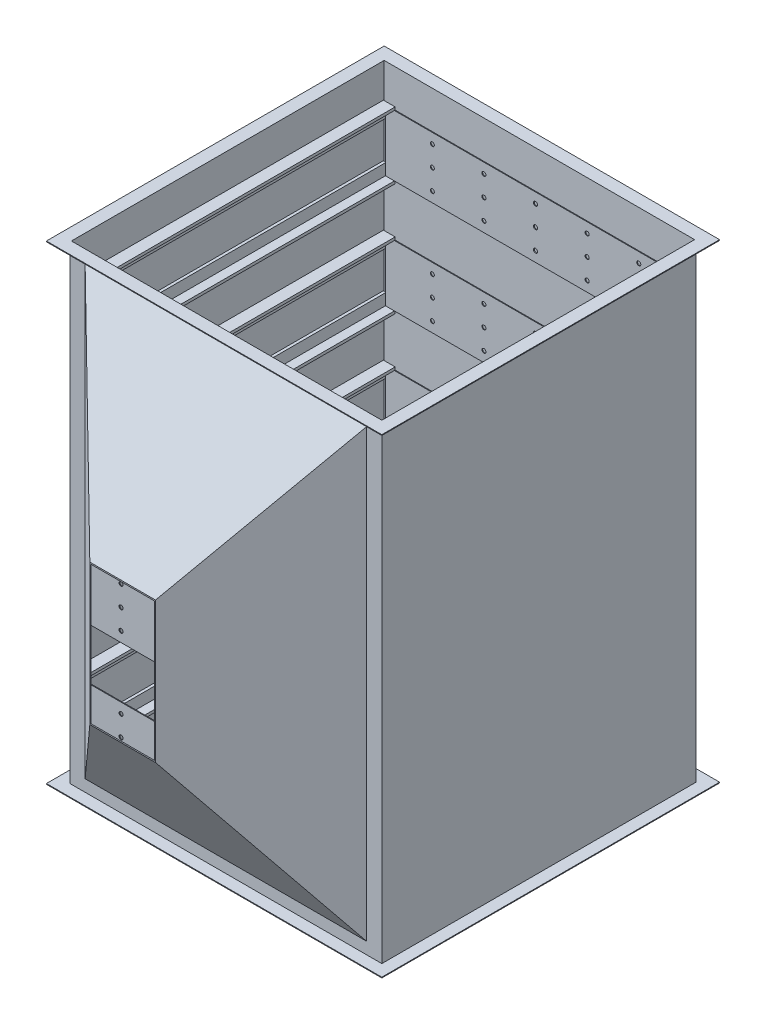
SolidWorks part; units mm, degrees
ref_plane "Front Plane" through (0, 0, 0) normal (0, 0, 1) x (1, 0, 0)
ref_plane "Top Plane" through (0, 0, 0) normal (0, 1, 0) x (1, 0, 0)
ref_plane "Right Plane" through (0, 0, 0) normal (1, 0, 0) x (0, 0, -1)
sketch "Sketch1" plane through (0, 0, 0) normal (0, 0, 1) x (1, 0, 0)
  line L1 (-332.5, -500) -> (332.5, -500)
  line L2 (-332.5, -500) -> (-332.5, 500)
  line L3 (-332.5, 500) -> (332.5, 500)
  line L4 (332.5, -500) -> (332.5, 500)
  line L5 (0, 500) -> (0, -500) construction
  line L6 (-332.5, 0) -> (332.5, 0) construction
  point P0 (0, 0)
  dimension "D1" = 1000
  dimension "D2" = 665
extrude "Boss-Extrude1" add sketch "Sketch1" along normal blind 670
sketch "Sketch2" plane through (0, 0, 670) normal (0, 0, 1) x (1, 0, 0)
  line L1 (-300, -475) -> (300, -475)
  line L2 (-300, -475) -> (-300, 475)
  line L3 (-300, 475) -> (300, 475)
  line L4 (300, -475) -> (300, 475)
  line L5 (0, 475) -> (0, -475) construction
  line L6 (-300, 0) -> (300, 0) construction
  point P0 (0, 0)
  dimension "D1" = 950
  dimension "D2" = 600
ref_plane "Plane1" through (0, 0, 890) normal (0, 0, 1) x (1, 0, 0)
sketch "Sketch3" plane through (0, 0, 890) normal (0, 0, 1) x (1, 0, 0)
  line L1 (-70, -150) -> (70, -150)
  line L2 (-70, -150) -> (-70, 150)
  line L3 (-70, 150) -> (70, 150)
  line L4 (70, -150) -> (70, 150)
  line L5 (0, 150) -> (0, -150) construction
  line L6 (-70, 0) -> (70, 0) construction
  point P0 (0, 0)
  dimension "D1" = 300
  dimension "D2" = 140
loft "Loft1" add profiles "Sketch2", "Sketch3" connector at (-300, 475, 670) connector at (-70, 150, 890)
sketch "Sketch4" plane through (0, 500, 0) normal (0, 1, 0) x (1, 0, 0)
  line L0 (0, 0) -> (0, -670) construction
  line L1 (332.5, 0) -> (-332.5, 0) construction
  line L2 (332.5, -670) -> (-332.5, -670) construction
  line L17 (357.5, -695) -> (357.5, 25)
  line L18 (-357.5, -695) -> (357.5, -695)
  line L19 (-357.5, 25) -> (-357.5, -695)
  line L20 (357.5, 25) -> (-357.5, 25)
  line L21 (357.5, -695) -> (357.5, 25)
  line L22 (-357.5, -695) -> (357.5, -695)
  line L23 (-357.5, 25) -> (-357.5, -695)
  line L24 (357.5, 25) -> (-357.5, 25)
  dimension "D1" = 25
extrude "Boss-Extrude2" add sketch "Sketch4" along normal blind 1.5875
ref_plane "Plano3" through (0, 0, 0) normal (0, -1, 0) x (-1, 0, 0)
mirror "Simetría4" about plane through (0, 0, 0) normal (0, -1, 0) of "Boss-Extrude2"
shell "Shell1" thickness 1.5875 removed face at (0, -501.5875, 335) removed face at (0, 0, 890) removed face at (0, 501.5875, 335)
sketch "Croquis1" plane through (0, 0, 668.4125) normal (0, 0, -1) x (-1, 0, 0)
  line L0 (-325, 401.4331) -> (325, 401.4331) construction
  line L5 (-325, 423.0998) -> (325, 423.0998)
  line L6 (-325, 423.0998) -> (-325, 379.7664)
  line L7 (-325, 379.7664) -> (325, 379.7664) construction
  line L8 (325, 423.0998) -> (325, 379.7664)
  line L9 (-107, 423.0998) -> (-107, 293.0998) construction
  line L26 (-325, 379.7664) -> (325, 379.7664) construction
  line L27 (-325, 379.7664) -> (-325, 336.4331)
  line L28 (-325, 336.4331) -> (325, 336.4331) construction
  line L29 (325, 379.7664) -> (325, 336.4331)
  line L30 (-325, 336.4331) -> (325, 336.4331) construction
  line L31 (-325, 336.4331) -> (-325, 293.0998)
  line L32 (-325, 293.0998) -> (325, 293.0998)
  line L33 (325, 336.4331) -> (325, 293.0998)
  line L34 (325, 358.0998) -> (-325, 358.0998) construction
  line L35 (-325, 314.7664) -> (325, 314.7664) construction
  line L36 (0, 293.0998) -> (0, 423.0998) construction
  line L37 (-215, 423.0998) -> (-215, 293.0998) construction
  line L38 (1, 423.0998) -> (1, 293.0998) construction
  line L39 (109, 423.0998) -> (109, 293.0998) construction
  line L40 (217, 423.0998) -> (217, 293.0998) construction
  line L41 (325, 423.0998) -> (325, 293.0998) construction
  line L44 (-325, 183.0998) -> (325, 183.0998)
  line L45 (-325, 183.0998) -> (-325, 139.7664)
  line L46 (325, 183.0998) -> (325, 139.7664)
  line L47 (-325, 139.7664) -> (-325, 96.4331)
  line L48 (325, 139.7664) -> (325, 96.4331)
  line L49 (-325, 96.4331) -> (-325, 53.0998)
  line L50 (-325, 53.0998) -> (325, 53.0998)
  line L51 (325, 96.4331) -> (325, 53.0998)
  line L52 (-325, 161.4331) -> (325, 161.4331) construction
  line L53 (-325, 139.7664) -> (325, 139.7664) construction
  line L54 (-107, 183.0998) -> (-107, 53.0998) construction
  line L55 (-325, 139.7664) -> (325, 139.7664) construction
  line L56 (-325, 96.4331) -> (325, 96.4331) construction
  line L57 (-325, 96.4331) -> (325, 96.4331) construction
  line L58 (325, 118.0998) -> (-325, 118.0998) construction
  line L59 (-325, 74.7664) -> (325, 74.7664) construction
  line L60 (0, 53.0998) -> (0, 183.0998) construction
  line L61 (-215, 183.0998) -> (-215, 53.0998) construction
  line L62 (1, 183.0998) -> (1, 53.0998) construction
  line L63 (109, 183.0998) -> (109, 53.0998) construction
  line L64 (217, 183.0998) -> (217, 53.0998) construction
  line L65 (325, 183.0998) -> (325, 53.0998) construction
  line L66 (-325, -56.9002) -> (325, -56.9002)
  line L67 (-325, -56.9002) -> (-325, -100.2336)
  line L68 (325, -56.9002) -> (325, -100.2336)
  line L69 (-325, -100.2336) -> (-325, -143.5669)
  line L70 (325, -100.2336) -> (325, -143.5669)
  line L71 (-325, -143.5669) -> (-325, -186.9002)
  line L72 (-325, -186.9002) -> (325, -186.9002)
  line L73 (325, -143.5669) -> (325, -186.9002)
  line L74 (-325, -78.5669) -> (325, -78.5669) construction
  line L75 (-325, -100.2336) -> (325, -100.2336) construction
  line L76 (-107, -56.9002) -> (-107, -186.9002) construction
  line L77 (-325, -100.2336) -> (325, -100.2336) construction
  line L78 (-325, -143.5669) -> (325, -143.5669) construction
  line L79 (-325, -143.5669) -> (325, -143.5669) construction
  line L80 (325, -121.9002) -> (-325, -121.9002) construction
  line L81 (-325, -165.2336) -> (325, -165.2336) construction
  line L82 (0, -186.9002) -> (0, -56.9002) construction
  line L83 (-215, -56.9002) -> (-215, -186.9002) construction
  line L84 (1, -56.9002) -> (1, -186.9002) construction
  line L85 (109, -56.9002) -> (109, -186.9002) construction
  line L86 (217, -56.9002) -> (217, -186.9002) construction
  line L87 (325, -56.9002) -> (325, -186.9002) construction
  line L88 (-325, -296.9002) -> (325, -296.9002)
  line L89 (-325, -296.9002) -> (-325, -340.2336)
  line L90 (325, -296.9002) -> (325, -340.2336)
  line L91 (-325, -340.2336) -> (-325, -383.5669)
  line L92 (325, -340.2336) -> (325, -383.5669)
  line L93 (-325, -383.5669) -> (-325, -426.9002)
  line L94 (-325, -426.9002) -> (325, -426.9002)
  line L95 (325, -383.5669) -> (325, -426.9002)
  line L96 (-325, -318.5669) -> (325, -318.5669) construction
  line L97 (-325, -340.2336) -> (325, -340.2336) construction
  line L98 (-107, -296.9002) -> (-107, -426.9002) construction
  line L99 (-325, -340.2336) -> (325, -340.2336) construction
  line L100 (-325, -383.5669) -> (325, -383.5669) construction
  line L101 (-325, -383.5669) -> (325, -383.5669) construction
  line L102 (325, -361.9002) -> (-325, -361.9002) construction
  line L103 (-325, -405.2336) -> (325, -405.2336) construction
  line L104 (0, -426.9002) -> (0, -296.9002) construction
  line L105 (-215, -296.9002) -> (-215, -426.9002) construction
  line L106 (1, -296.9002) -> (1, -426.9002) construction
  line L107 (109, -296.9002) -> (109, -426.9002) construction
  line L108 (217, -296.9002) -> (217, -426.9002) construction
  line L109 (325, -296.9002) -> (325, -426.9002) construction
  circle A39 centre (-215, 401.4331) radius 4.3656
  circle A40 centre (-215, 358.0998) radius 4.3656
  circle A41 centre (-215, 314.7664) radius 4.3656
  circle A42 centre (-105, 401.4331) radius 4.3656
  circle A43 centre (-105, 358.0998) radius 4.3656
  circle A44 centre (-105, 314.7664) radius 4.3656
  circle A45 centre (5, 401.4331) radius 4.3656
  circle A46 centre (5, 358.0998) radius 4.3656
  circle A47 centre (5, 314.7664) radius 4.3656
  circle A48 centre (115, 401.4331) radius 4.3656
  circle A49 centre (115, 358.0998) radius 4.3656
  circle A50 centre (115, 314.7664) radius 4.3656
  circle A51 centre (225, 401.4331) radius 4.3656
  circle A52 centre (225, 358.0998) radius 4.3656
  circle A53 centre (225, 314.7664) radius 4.3656
  circle A54 centre (-215, 161.4331) radius 4.3656
  circle A55 centre (-215, 118.0998) radius 4.3656
  circle A56 centre (-215, 74.7664) radius 4.3656
  circle A57 centre (-105, 161.4331) radius 4.3656
  circle A58 centre (-105, 118.0998) radius 4.3656
  circle A59 centre (-105, 74.7664) radius 4.3656
  circle A60 centre (5, 161.4331) radius 4.3656
  circle A61 centre (5, 118.0998) radius 4.3656
  circle A62 centre (5, 74.7664) radius 4.3656
  circle A63 centre (115, 161.4331) radius 4.3656
  circle A64 centre (115, 118.0998) radius 4.3656
  circle A65 centre (115, 74.7664) radius 4.3656
  circle A66 centre (225, 161.4331) radius 4.3656
  circle A67 centre (225, 118.0998) radius 4.3656
  circle A68 centre (225, 74.7664) radius 4.3656
  circle A69 centre (-215, -78.5669) radius 4.3656
  circle A70 centre (-215, -121.9002) radius 4.3656
  circle A71 centre (-215, -165.2336) radius 4.3656
  circle A72 centre (-105, -78.5669) radius 4.3656
  circle A73 centre (-105, -121.9002) radius 4.3656
  circle A74 centre (-105, -165.2336) radius 4.3656
  circle A75 centre (5, -78.5669) radius 4.3656
  circle A76 centre (5, -121.9002) radius 4.3656
  circle A77 centre (5, -165.2336) radius 4.3656
  circle A78 centre (115, -78.5669) radius 4.3656
  circle A79 centre (115, -121.9002) radius 4.3656
  circle A80 centre (115, -165.2336) radius 4.3656
  circle A81 centre (225, -78.5669) radius 4.3656
  circle A82 centre (225, -121.9002) radius 4.3656
  circle A83 centre (225, -165.2336) radius 4.3656
  circle A84 centre (-215, -318.5669) radius 4.3656
  circle A85 centre (-215, -361.9002) radius 4.3656
  circle A86 centre (-215, -405.2336) radius 4.3656
  circle A87 centre (-105, -318.5669) radius 4.3656
  circle A88 centre (-105, -361.9002) radius 4.3656
  circle A89 centre (-105, -405.2336) radius 4.3656
  circle A90 centre (5, -318.5669) radius 4.3656
  circle A91 centre (5, -361.9002) radius 4.3656
  circle A92 centre (5, -405.2336) radius 4.3656
  circle A93 centre (115, -318.5669) radius 4.3656
  circle A94 centre (115, -361.9002) radius 4.3656
  circle A95 centre (115, -405.2336) radius 4.3656
  circle A96 centre (225, -318.5669) radius 4.3656
  circle A97 centre (225, -361.9002) radius 4.3656
  circle A98 centre (225, -405.2336) radius 4.3656
  dimension "D5" = 4
  dimension "D4" = 8.7312
  dimension "D2" = 650
  dimension "D3" = 110
  dimension "D1" = 130
extrude "Saliente-Extruir1" add sketch "Croquis1" along normal blind 1.5875 separate body
ref_plane "Plano2" through (0, 0, 335.7937) normal (0, 0, 1) x (1, 0, 0)
mirror "Simetría3" about plane through (0, 0, 335.7937) normal (0, 0, 1) of bodies 105 127 128 126 104 106 107 108
sketch "Croquis4" plane through (0, 0, 668.4125) normal (0, 0, -1) x (-1, 0, 0)
  line L0 (305.9125, 423.0998) -> (305.9125, 429.0123)
  line L1 (325, 423.0998) -> (-325, 423.0998) construction
  line L2 (305.9125, 429.0123) -> (330.9125, 429.0123)
  line L3 (330.9125, 501.5875) -> (330.9125, -501.5875) construction
  line L4 (330.9125, 429.0123) -> (330.9125, 399.0123)
  line L5 (330.9125, 399.0123) -> (325, 399.0123)
  line L6 (325, 293.0998) -> (325, 423.0998) construction
  line L7 (325, 399.0123) -> (325, 423.0998)
  line L8 (325, 423.0998) -> (305.9125, 423.0998)
  line L9 (0, 0) -> (0, 501.5875) construction
  line L10 (-330.9125, 501.5875) -> (330.9125, 501.5875) construction
  line L11 (325, 358.0998) -> (-325, 358.0998) construction
  line L12 (-325, 423.0998) -> (-325, 293.0998) construction
  line L13 (325, 293.0998) -> (305.9125, 293.0998)
  line L14 (325, 317.1873) -> (325, 293.0998)
  line L15 (330.9125, 317.1873) -> (325, 317.1873)
  line L16 (330.9125, 287.1873) -> (330.9125, 317.1873)
  line L17 (305.9125, 287.1873) -> (330.9125, 287.1873)
  line L18 (305.9125, 293.0998) -> (305.9125, 287.1873)
  line L19 (305.9125, 183.0998) -> (305.9125, 189.0123)
  line L20 (305.9125, 189.0123) -> (330.9125, 189.0123)
  line L21 (330.9125, 189.0123) -> (330.9125, 159.0123)
  line L22 (330.9125, 159.0123) -> (325, 159.0123)
  line L23 (325, 159.0123) -> (325, 183.0998)
  line L24 (325, 183.0998) -> (305.9125, 183.0998)
  line L25 (325, 53.0998) -> (305.9125, 53.0998)
  line L26 (325, 77.1873) -> (325, 53.0998)
  line L27 (330.9125, 77.1873) -> (325, 77.1873)
  line L28 (330.9125, 47.1873) -> (330.9125, 77.1873)
  line L29 (305.9125, 47.1873) -> (330.9125, 47.1873)
  line L30 (305.9125, 53.0998) -> (305.9125, 47.1873)
  line L31 (305.9125, -56.9002) -> (305.9125, -50.9877)
  line L32 (305.9125, -50.9877) -> (330.9125, -50.9877)
  line L33 (330.9125, -50.9877) -> (330.9125, -80.9877)
  line L34 (330.9125, -80.9877) -> (325, -80.9877)
  line L35 (325, -80.9877) -> (325, -56.9002)
  line L36 (325, -56.9002) -> (305.9125, -56.9002)
  line L37 (325, -186.9002) -> (305.9125, -186.9002)
  line L38 (325, -162.8127) -> (325, -186.9002)
  line L39 (330.9125, -162.8127) -> (325, -162.8127)
  line L40 (330.9125, -192.8127) -> (330.9125, -162.8127)
  line L41 (305.9125, -192.8127) -> (330.9125, -192.8127)
  line L42 (305.9125, -186.9002) -> (305.9125, -192.8127)
  line L43 (305.9125, -296.9002) -> (305.9125, -290.9877)
  line L44 (305.9125, -290.9877) -> (330.9125, -290.9877)
  line L45 (330.9125, -290.9877) -> (330.9125, -320.9877)
  line L46 (330.9125, -320.9877) -> (325, -320.9877)
  line L47 (325, -320.9877) -> (325, -296.9002)
  line L48 (325, -296.9002) -> (305.9125, -296.9002)
  line L49 (325, -426.9002) -> (305.9125, -426.9002)
  line L50 (325, -402.8127) -> (325, -426.9002)
  line L51 (330.9125, -402.8127) -> (325, -402.8127)
  line L52 (330.9125, -432.8127) -> (330.9125, -402.8127)
  line L53 (305.9125, -432.8127) -> (330.9125, -432.8127)
  line L54 (305.9125, -426.9002) -> (305.9125, -432.8127)
  line L55 (-325, 53.0998) -> (325, 53.0998) construction
  line L56 (-305.9125, -426.9002) -> (-305.9125, -432.8127)
  line L57 (-305.9125, -432.8127) -> (-330.9125, -432.8127)
  line L58 (-330.9125, -432.8127) -> (-330.9125, -402.8127)
  line L59 (-330.9125, -402.8127) -> (-325, -402.8127)
  line L60 (-325, -402.8127) -> (-325, -426.9002)
  line L61 (-325, -426.9002) -> (-305.9125, -426.9002)
  line L62 (-325, -296.9002) -> (-305.9125, -296.9002)
  line L63 (-325, -320.9877) -> (-325, -296.9002)
  line L64 (-330.9125, -320.9877) -> (-325, -320.9877)
  line L65 (-330.9125, -290.9877) -> (-330.9125, -320.9877)
  line L66 (-305.9125, -290.9877) -> (-330.9125, -290.9877)
  line L67 (-305.9125, -296.9002) -> (-305.9125, -290.9877)
  line L68 (-305.9125, -186.9002) -> (-305.9125, -192.8127)
  line L69 (-305.9125, -192.8127) -> (-330.9125, -192.8127)
  line L70 (-330.9125, -192.8127) -> (-330.9125, -162.8127)
  line L71 (-330.9125, -162.8127) -> (-325, -162.8127)
  line L72 (-325, -162.8127) -> (-325, -186.9002)
  line L73 (-325, -186.9002) -> (-305.9125, -186.9002)
  line L74 (-325, -56.9002) -> (-305.9125, -56.9002)
  line L75 (-325, -80.9877) -> (-325, -56.9002)
  line L76 (-330.9125, -80.9877) -> (-325, -80.9877)
  line L77 (-330.9125, -50.9877) -> (-330.9125, -80.9877)
  line L78 (-305.9125, -50.9877) -> (-330.9125, -50.9877)
  line L79 (-305.9125, -56.9002) -> (-305.9125, -50.9877)
  line L80 (-305.9125, 53.0998) -> (-305.9125, 47.1873)
  line L81 (-305.9125, 47.1873) -> (-330.9125, 47.1873)
  line L82 (-330.9125, 47.1873) -> (-330.9125, 77.1873)
  line L83 (-330.9125, 77.1873) -> (-325, 77.1873)
  line L84 (-325, 77.1873) -> (-325, 53.0998)
  line L85 (-325, 53.0998) -> (-305.9125, 53.0998)
  line L86 (-325, 183.0998) -> (-305.9125, 183.0998)
  line L87 (-325, 159.0123) -> (-325, 183.0998)
  line L88 (-330.9125, 159.0123) -> (-325, 159.0123)
  line L89 (-330.9125, 189.0123) -> (-330.9125, 159.0123)
  line L90 (-305.9125, 189.0123) -> (-330.9125, 189.0123)
  line L91 (-305.9125, 183.0998) -> (-305.9125, 189.0123)
  line L92 (-305.9125, 293.0998) -> (-305.9125, 287.1873)
  line L93 (-305.9125, 287.1873) -> (-330.9125, 287.1873)
  line L94 (-330.9125, 287.1873) -> (-330.9125, 317.1873)
  line L95 (-330.9125, 317.1873) -> (-325, 317.1873)
  line L96 (-325, 317.1873) -> (-325, 293.0998)
  line L97 (-325, 293.0998) -> (-305.9125, 293.0998)
  line L98 (-325, 423.0998) -> (-305.9125, 423.0998)
  line L99 (-325, 399.0123) -> (-325, 423.0998)
  line L100 (-330.9125, 399.0123) -> (-325, 399.0123)
  line L101 (-330.9125, 429.0123) -> (-330.9125, 399.0123)
  line L102 (-305.9125, 429.0123) -> (-330.9125, 429.0123)
  line L103 (-305.9125, 423.0998) -> (-305.9125, 429.0123)
  dimension "D1" = 25
  dimension "D2" = 30
  dimension "D3" = 4
extrude "Saliente-Extruir2" add sketch "Croquis4" along normal offset from surface (665.2375 mm away) 1.5875 up to face at (0, 0, 1.5875)
